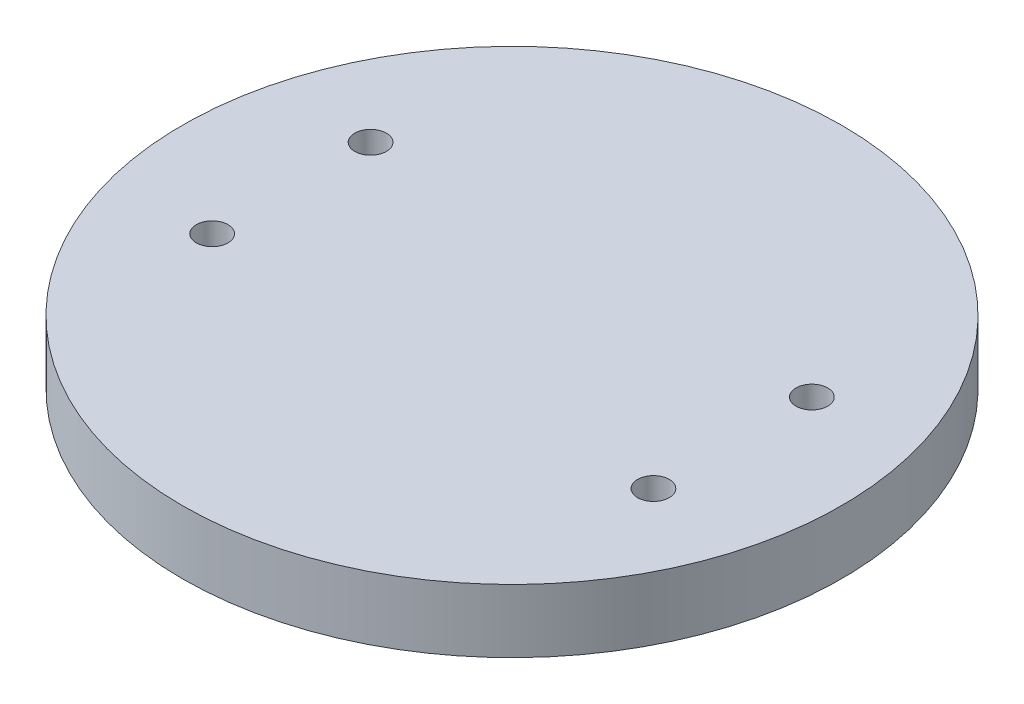
SolidWorks part; units mm, degrees
ref_plane "Front Plane" through (0, 0, 0) normal (0, 0, 1) x (1, 0, 0)
ref_plane "Top Plane" through (0, 0, 0) normal (0, 1, 0) x (1, 0, 0)
ref_plane "Right Plane" through (0, 0, 0) normal (1, 0, 0) x (0, 0, -1)
sketch "Sketch1" plane through (0, 0, 0) normal (0, 1, 0) x (1, 0, 0)
  circle A0 centre (0, 0) radius 66.04
  dimension "D1" = 132.08
extrude "Boss-Extrude1" add sketch "Sketch1" along normal blind 12.7
sketch "Sketch2" plane through (0, 12.7, 0) normal (0, 1, 0) x (1, 0, 0)
  line L0 (-72.7941, 0) -> (72.3878, 0) construction
  line L1 (0, 70.7385) -> (0, -72.4581) construction
  circle A0 centre (-44.2148, 15.875) radius 3.175
  circle A1 centre (-44.2148, -15.875) radius 3.175
  circle A2 centre (44.2148, -15.875) radius 3.175
  circle A3 centre (44.2148, 15.875) radius 3.175
  dimension "D1" = 6.35
  dimension "D2" = 15.875
extrude "Cut-Extrude1" cut sketch "Sketch2" against normal through all
